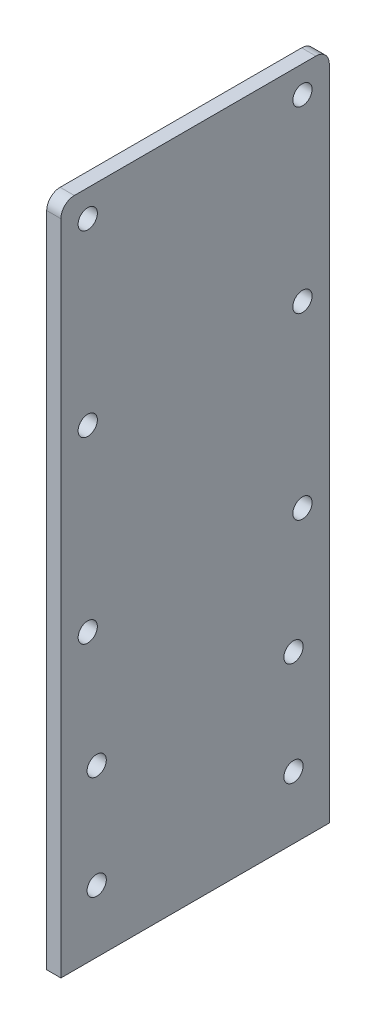
SolidWorks part; units mm, degrees
ref_plane "Front Plane" through (0, 0, 0) normal (0, 0, 1) x (1, 0, 0)
ref_plane "Top Plane" through (0, 0, 0) normal (0, 1, 0) x (1, 0, 0)
ref_plane "Right Plane" through (0, 0, 0) normal (1, 0, 0) x (0, 0, -1)
sketch "Sketch1" plane through (0, 0, 0) normal (1, 0, 0) x (0, 0, -1)
  line L0 (0, -75) -> (0, 75) construction
  line L1 (-30, -75) -> (30, -75)
  line L2 (-30, -75) -> (-30, 75)
  line L3 (-30, 75) -> (30, 75)
  line L4 (30, -75) -> (30, 75)
  line L5 (-30, -75) -> (30, 75) construction
  line L6 (-30, 75) -> (30, -75) construction
  circle A0 centre (-22, -61.025) radius 2.15
  circle A1 centre (22, -61.025) radius 2.15
  circle A2 centre (-22, -37.851) radius 2.15
  circle A3 centre (22, -37.851) radius 2.15
  circle A4 centre (-24, 69) radius 2.15
  circle A5 centre (-24, 29) radius 2.15
  circle A6 centre (-24, -11) radius 2.15
  circle A7 centre (24, -11) radius 2.15
  circle A8 centre (24, 29) radius 2.15
  circle A9 centre (24, 69) radius 2.15
  point P0 (0, 0)
  dimension "D4" = 4.3
  dimension "D7" = 4.3
  dimension "D8" = 4.3
  dimension "D1" = 150
  dimension "D2" = 60
  dimension "D3" = 13.975
  dimension "D5" = 8
  dimension "D6" = 37.149
  dimension "D9" = 6
  dimension "D10" = 6
  dimension "D11" = 3
extrude "Boss-Extrude1" add sketch "Sketch1" along normal blind 3.175
fillet "Fillet1" radius 3 2 edges at (1.5875, 75, -30) (1.5875, 75, 30)
